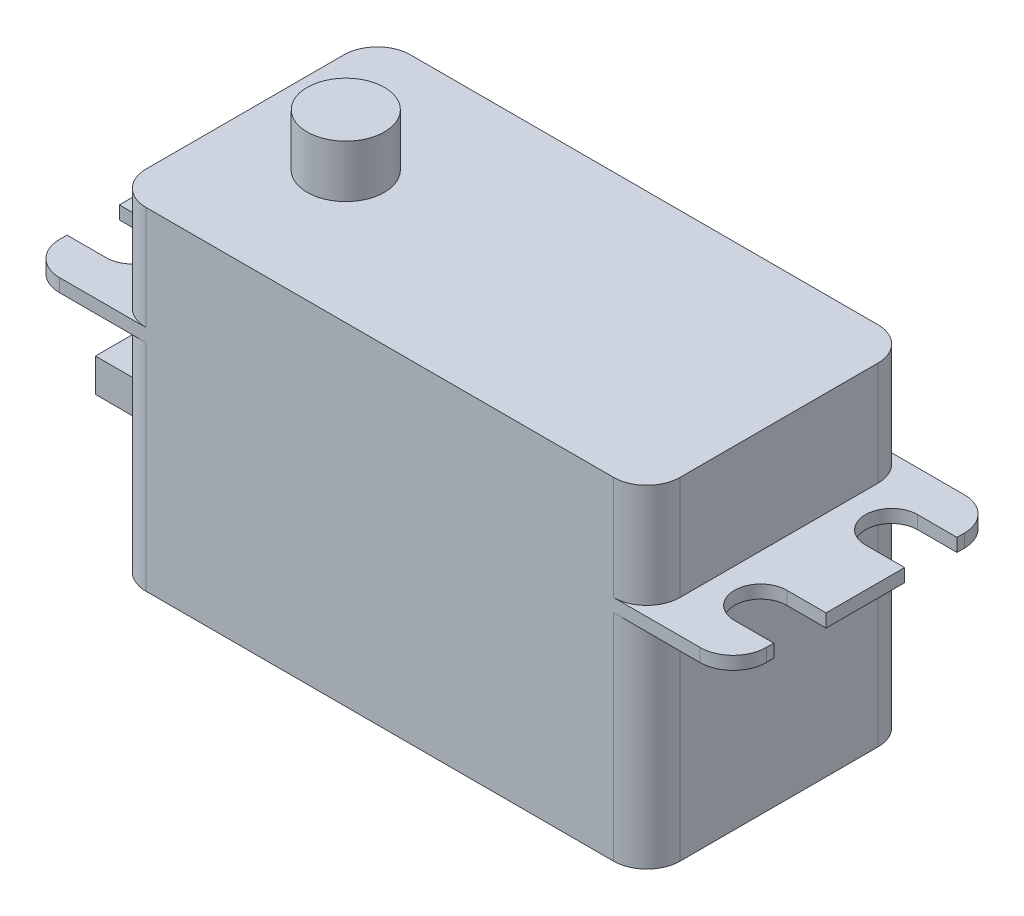
SolidWorks part; units mm, degrees
ref_plane "Front Plane" through (0, 0, 0) normal (0, 0, 1) x (1, 0, 0)
ref_plane "Top Plane" through (0, 0, 0) normal (0, 1, 0) x (1, 0, 0)
ref_plane "Right Plane" through (0, 0, 0) normal (1, 0, 0) x (0, 0, -1)
sketch "Sketch1" plane through (0, 0, 0) normal (0, 1, 0) x (1, 0, 0)
  line L0 (-16.17, 0) -> (16.17, 0) construction
  line L1 (-24.46, -10.1) -> (24.46, -10.1)
  line L2 (-27, -7.56) -> (-27, 7.56)
  line L3 (-24.46, 10.1) -> (24.46, 10.1)
  line L4 (27, -7.56) -> (27, 7.56)
  line L5 (-27, -10.1) -> (27, 10.1) construction
  line L6 (-27, 10.1) -> (27, -10.1) construction
  line L7 (0, -11.11) -> (0, 11.11) construction
  line L8 (24, 3) -> (27, 3)
  line L9 (24, 7) -> (27, 7)
  line L10 (27, 7) -> (27, 3)
  line L11 (24, -3) -> (27, -3)
  line L12 (24, -7) -> (27, -7)
  line L13 (27, -7) -> (27, -3)
  line L14 (-24, 7) -> (-27, 7)
  line L15 (-24, 3) -> (-27, 3)
  line L16 (-27, 3) -> (-27, 7)
  line L17 (-24, -7) -> (-27, -7)
  line L18 (-24, -3) -> (-27, -3)
  line L19 (-27, -3) -> (-27, -7)
  arc A0 (24, 7) -> (24, 3) centre (24, 5) ccw
  arc A1 (24, -7) -> (24, -3) centre (24, -5) cw
  arc A2 (-24, -7) -> (-24, -3) centre (-24, -5) ccw
  arc A3 (-24, 7) -> (-24, 3) centre (-24, 5) cw
  arc A4 (-24.46, -10.1) -> (-27, -7.56) centre (-24.46, -7.56) cw
  arc A5 (24.46, -10.1) -> (27, -7.56) centre (24.46, -7.56) ccw
  arc A6 (24.46, 10.1) -> (27, 7.56) centre (24.46, 7.56) cw
  arc A7 (-27, 7.56) -> (-24.46, 10.1) centre (-24.46, 7.56) cw
  point P0 (0, 0)
  dimension "D3" = 4
  dimension "D6" = 2.54
  dimension "D1" = 54
  dimension "D2" = 20.2
  dimension "D4" = 48
  dimension "D5" = 10
extrude "Boss-Extrude1" add sketch "Sketch1" along normal blind 1 contours A7 L2 L14 A3 L15 L18 A2 L17 A4 L1 A5 L4 L12 A1 L11 L8 A0 L9 A6 L3 region at (0, 0, 0)
sketch "Sketch3" plane through (0, 1, 0) normal (0, 1, 0) x (1, 0, 0)
  line L1 (-17.86, -10.1) -> (17.86, -10.1)
  line L2 (-20.4, -7.56) -> (-20.4, 7.56)
  line L3 (-17.86, 10.1) -> (17.86, 10.1)
  line L4 (20.4, -7.56) -> (20.4, 7.56)
  line L5 (-20.4, -10.1) -> (20.4, 10.1) construction
  line L6 (-20.4, 10.1) -> (20.4, -10.1) construction
  arc A0 (-17.86, -10.1) -> (-20.4, -7.56) centre (-17.86, -7.56) cw
  arc A1 (17.86, -10.1) -> (20.4, -7.56) centre (17.86, -7.56) ccw
  arc A2 (17.86, 10.1) -> (20.4, 7.56) centre (17.86, 7.56) cw
  arc A3 (-20.4, 7.56) -> (-17.86, 10.1) centre (-17.86, 7.56) cw
  point P0 (0, 0)
  dimension "D3" = 2.54
  dimension "D1" = 40.8
  dimension "D2" = 20.2
extrude "Boss-Extrude2" add sketch "Sketch3" along normal blind 7.95
sketch "Sketch4" plane through (0, 0, 0) normal (0, -1, 0) x (1, 0, 0)
  line L1 (-17.86, -10.1) -> (17.86, -10.1)
  line L2 (-20.4, -7.56) -> (-20.4, 7.56)
  line L3 (-17.86, 10.1) -> (17.86, 10.1)
  line L4 (20.4, -7.56) -> (20.4, 7.56)
  line L5 (-20.4, -10.1) -> (20.4, 10.1) construction
  line L6 (-20.4, 10.1) -> (20.4, -10.1) construction
  arc A0 (-17.86, -10.1) -> (-20.4, -7.56) centre (-17.86, -7.56) cw
  arc A1 (17.86, -10.1) -> (20.4, -7.56) centre (17.86, -7.56) ccw
  arc A2 (17.86, 10.1) -> (20.4, 7.56) centre (17.86, 7.56) cw
  arc A3 (-20.4, 7.56) -> (-17.86, 10.1) centre (-17.86, 7.56) cw
  point P0 (0, 0)
  dimension "D3" = 2.54
  dimension "D1" = 20.2
  dimension "D2" = 40.8
extrude "Boss-Extrude3" add sketch "Sketch4" along normal blind 16.45
sketch "Sketch5" plane through (-20.4, 0, 0) normal (-1, 0, 0) x (0, 0, 1)
  line L0 (-0.8843, -9.5287) -> (-0.8843, -11.2259)
  line L1 (-3.81, -11.6473) -> (3.81, -11.6473)
  line L2 (-3.81, -11.6473) -> (-3.81, -9.1073)
  line L3 (-3.81, -9.1073) -> (3.81, -9.1073)
  line L4 (3.81, -11.6473) -> (3.81, -9.1073)
  line L5 (-3.4243, -9.5287) -> (-1.6557, -9.5287)
  line L6 (-3.4243, -9.5287) -> (-3.4243, -11.2259)
  line L7 (-3.4243, -11.2259) -> (-1.6557, -11.2259)
  line L8 (-1.6557, -9.5287) -> (-1.6557, -11.2259)
  line L9 (-0.8843, -9.5287) -> (0.8843, -9.5287)
  line L10 (0.8843, -9.5287) -> (0.8843, -11.2259)
  line L11 (-0.8843, -11.2259) -> (0.8843, -11.2259)
  line L12 (1.6557, -9.5287) -> (1.6557, -11.2259)
  line L13 (1.6557, -9.5287) -> (3.4243, -9.5287)
  line L14 (3.4243, -9.5287) -> (3.4243, -11.2259)
  line L15 (1.6557, -11.2259) -> (3.4243, -11.2259)
  point P8 (0, -11.6473)
  point P18 (-3.4243, -10.3773)
  point P19 (-3.81, -10.3773)
  point P20 (0, -11.2259)
  dimension "D2" = 2.54
  dimension "D3" = 2.54
  dimension "D4" = 7.62
  dimension "D1" = 3
extrude "Boss-Extrude4" add sketch "Sketch5" along normal blind 7.62
sketch "Sketch6" plane through (0, 8.95, 0) normal (0, 1, 0) x (1, 0, 0)
  circle A0 centre (-12.7, 0) radius 2.95
  dimension "D1" = 5.9
  dimension "D2" = 12.7
extrude "Boss-Extrude5" add sketch "Sketch6" along normal blind 4
other "CPoint1" parameters "Diameter"=25.4, "StubLength"=38.1
ref_axis "Axis1" through (-38.02, -11.2259, -3.4243) along (1, 0, 0)
other "CPoint2" parameters "Diameter"=25.4, "StubLength"=38.1
ref_axis "Axis2" through (-38.02, -11.2259, -0.8843) along (1, 0, 0)
other "CPoint3" parameters "Diameter"=25.4, "StubLength"=38.1
ref_axis "Axis3" through (-38.02, -11.2259, 1.6557) along (1, 0, 0)
equation "\"Bodytube_OD\" = 6.17in"
equation "\"Bodytube_ID\" = 5.998in"
equation "\"Motor_OD\" = 4in"
equation "\"Fwd_Tube_Length\" = 40in"
equation "\"Mid_Tube_Length\" = 1in"
equation "\"Aft_Section_Length\"= 39in"
equation "\"AB_Coupler_OD_Length\"= 1in"
equation "\"AB_Coupling_Section_Length\"= 0.375in"
equation "\"AB_Coupler_Length\"= \"AB_Coupler_OD_Length\" + \"AB_Coupling_Section_Length\" * 2"
equation "\"Cutout_Angle\" = 80"
equation "\"AB_Paddle_Height\" = 0.375in"
equation "\"AB_Coupler_Num_Screws\"= 6"
equation "\"Num_Cutouts\" = 3"
equation "\"AB_Coupler_OD\"= 6.17in"
equation "\"AB_Coupler_ID\"= 5.75in"
equation "\"AB_Coupler_Surface_Diameter\"= 5.998in"
equation "\"AB_Coupling_Screw_Diameter\"= 0.1065in"
equation "\"AB_Central_Bushing_Length\" = .75in"
equation "\"Lead_Screw_Dist\" = 2.25in"
equation "\"Lead_Screw_Diam\" = 11mm"
equation "\"Paddle_Pin_Offset\" = .25in"
equation "\"Paddle_Pin_Radius\" = 2.25in"
equation "\"Paddle_Gear_OD\" = 3.2in"
equation "\"Drive_Gear_OD\" = 1.7in"
equation "\"Fwd_BKHD_From_Top\" = 18in"
equation "\"Fin_Thickness\"= .118in"
equation "\"Guiderail_Cutout_Diameter\"= 1.5in"
equation "\"DB9_Hole_Dist\" = 25mm"
equation "\"Airbrakes_Wire_Hole_Dia\" = .25in"
equation "\"Airbrakes_Wire_Hole_Dist\" = 1.1in"
equation "\"Servo_Gear_Offset\" = 0.5in"
equation "\"D2@Sketch6\"=\"Servo_Gear_Offset\""
